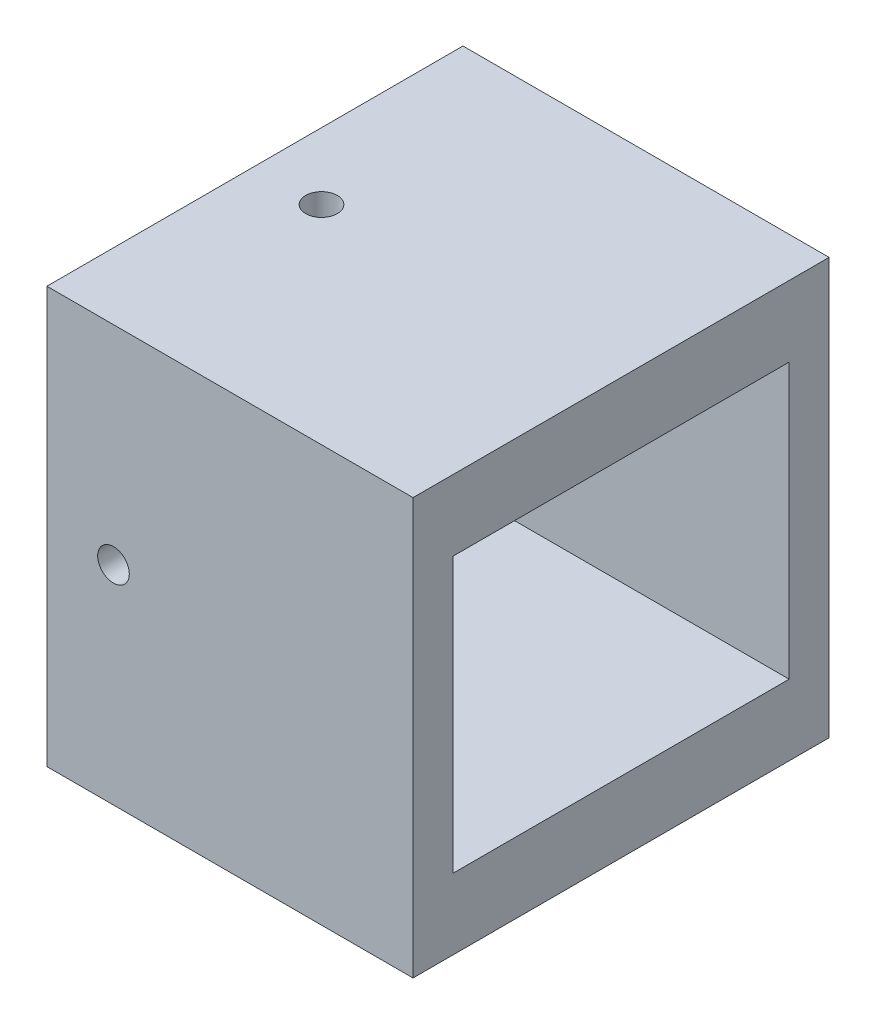
SolidWorks part; units mm, degrees
ref_plane "前视基准面" through (0, 0, 0) normal (0, 0, 1) x (1, 0, 0)
ref_plane "上视基准面" through (0, 0, 0) normal (0, 1, 0) x (1, 0, 0)
ref_plane "右视基准面" through (0, 0, 0) normal (1, 0, 0) x (0, 0, -1)
other "Configuration Table"
sketch "草图1" plane through (0, 0, 0) normal (1, 0, 0) x (0, 0, -1)
  line L1 (12.5, -12.5) -> (-12.5, -12.5)
  line L2 (12.5, -12.5) -> (12.5, 12.5)
  line L3 (12.5, 12.5) -> (-12.5, 12.5)
  line L4 (-12.5, -12.5) -> (-12.5, 12.5)
  line L5 (12.5, -12.5) -> (-12.5, 12.5) construction
  line L6 (12.5, 12.5) -> (-12.5, -12.5) construction
  line L7 (10.1, -8.25) -> (-10.1, -8.25)
  line L8 (10.1, -8.25) -> (10.1, 8.25)
  line L9 (10.1, 8.25) -> (-10.1, 8.25)
  line L10 (-10.1, -8.25) -> (-10.1, 8.25)
  line L11 (10.1, -8.25) -> (-10.1, 8.25) construction
  line L12 (10.1, 8.25) -> (-10.1, -8.25) construction
  circle A0 centre (0, 0) radius 0.5
  point P0 (0, 0)
  point P6 (-4.3103, -0.1766)
  point P14 (0, 0)
  point P16 (0, 0)
  dimension "D4" = 1
  dimension "D1" = 25
  dimension "D2" = 20.2
  dimension "D3" = 16.5
extrude "凸台-拉伸1" add sketch "草图1" along normal blind 20 contours L3 L4 L1 L2 | L9 L10 L7 L8
extrude "凸台-拉伸3" add sketch "草图1<3>" against normal blind 2 contours L1 L4 L3 L2
sketch "草图1<3>" plane through (0, 0, 0) normal (1, 0, 0) x (0, 0, -1) same geometry as "草图1"
extrude "切除-拉伸1" cut sketch "草图1<5>" against normal blind 0.1 contours A0 region at (0, 0, 0)
sketch "草图1<5>" plane through (0, 0, 0) normal (1, 0, 0) x (0, 0, -1) same geometry as "草图1"
sketch "草图2" plane through (0, -12.5, 0) normal (0, -1, 0) x (1, 0, 0)
  line L0 (-2, -12.5) -> (-2, 12.5) construction
  line L1 (2, 12.5) -> (2, -12.5) construction
  line L2 (20, 12.5) -> (-2, 12.5) construction
  line L3 (20, -12.5) -> (-2, -12.5) construction
  circle A0 centre (2, 0) radius 0.95
  point P10 (0, 0)
  dimension "D1" = 1.9
  dimension "D2" = 4
extrude "切除-拉伸2" cut sketch "草图2" against normal blind 4
sketch "草图3" plane through (0, 0, -12.5) normal (0, 0, -1) x (-1, 0, 0)
  line L0 (2, -12.5) -> (2, 12.5) construction
  line L1 (-2, 12.5) -> (-2, -12.5) construction
  line L2 (-20, 12.5) -> (2, 12.5) construction
  line L3 (-20, -12.5) -> (2, -12.5) construction
  circle A0 centre (-2, 0) radius 0.95
  point P10 (0, 0)
  dimension "D1" = 1.9
  dimension "D2" = 4
extrude "切除-拉伸3" cut sketch "草图3" against normal blind 4
sketch "草图4" plane through (0, 12.5, 0) normal (0, 1, 0) x (1, 0, 0)
  line L0 (-2, 12.5) -> (-2, -12.5) construction
  line L1 (2, 12.5) -> (2, -12.5) construction
  line L2 (20, 12.5) -> (-2, 12.5) construction
  line L3 (20, -12.5) -> (-2, -12.5) construction
  circle A0 centre (2, 0) radius 0.95
  dimension "D2" = 1.9
  dimension "D1" = 4
extrude "切除-拉伸4" cut sketch "草图4" against normal blind 4
sketch "草图5" plane through (0, 0, 12.5) normal (0, 0, 1) x (1, 0, 0)
  line L0 (-2, -12.5) -> (-2, 12.5) construction
  line L1 (2, 12.5) -> (2, -12.5) construction
  line L2 (20, 12.5) -> (-2, 12.5) construction
  line L3 (20, -12.5) -> (-2, -12.5) construction
  circle A0 centre (2, 0) radius 0.95
  point P10 (0, 0)
  dimension "D2" = 1.9
  dimension "D1" = 4
extrude "切除-拉伸5" cut sketch "草图5" against normal blind 4
sketch "草图6" plane through (-2, 0, 0) normal (-1, 0, 0) x (0, 0, 1)
  line L0 (12.5, -12.5) -> (12.5, 12.5) construction
  line L2 (12.5, 0) -> (6.1, 0) construction
  line L4 (-12.5, 0) -> (-6.1, 0) construction
  line L5 (-12.5, -12.5) -> (-12.5, 12.5) construction
  circle A0 centre (-6.1, 0) radius 0.75
  circle A1 centre (6.1, 0) radius 0.75
  point P5 (0, 0)
  point P11 (6.196, -1.7287)
  point P12 (-5.5798, 0)
  point P13 (6.0248, 0)
  point P14 (7.5, 0)
  point P16 (11.5704, 2.8926)
  point P17 (15.7467, 2.0368)
  dimension "D2" = 1.5
  dimension "D1" = 6.4
extrude "切除-拉伸6" cut sketch "草图6" against normal up to surface (2 mm away) up to face at (0, 0, -0.5)
